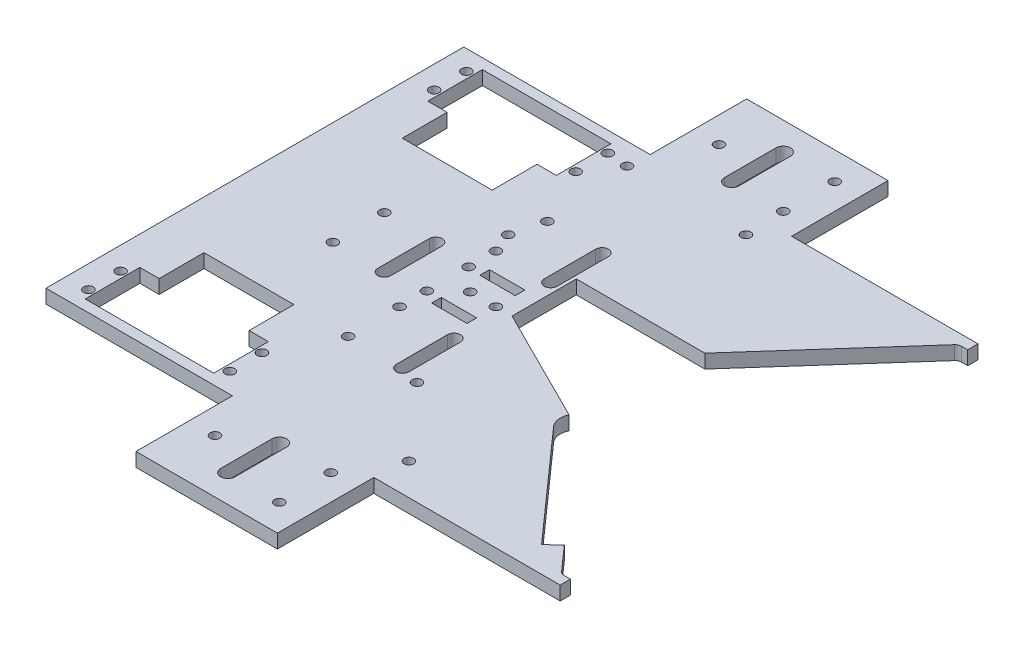
SolidWorks part; units mm, degrees
ref_plane "Front Plane" through (0, 0, 0) normal (0, 0, 1) x (1, 0, 0)
ref_plane "Top Plane" through (0, 0, 0) normal (0, 1, 0) x (1, 0, 0)
ref_plane "Right Plane" through (0, 0, 0) normal (1, 0, 0) x (0, 0, -1)
sketch "Sketch2" plane through (0, 0, 0) normal (0, 1, 0) x (1, 0, 0)
  line L2 (0, 0) -> (0, 65)
  line L3 (0, 65) -> (58, 65)
  line L4 (160, 0) -> (160, 65)
  line L8 (0, 0) -> (160, 0)
  line L9 (102, 65) -> (160, 65)
  line L11 (102, 65) -> (102, 95)
  line L12 (58, 65) -> (58, 95)
  line L13 (58, 95) -> (102, 95)
  dimension "D1" = 65
  dimension "D2" = 160
  dimension "D3" = 44
  dimension "D4" = 30
extrude "Boss-Extrude1" add sketch "Sketch2" along normal blind 4.3
mirror "Mirror1" about plane through (0, 4.3, 0) normal (0, 0, -1) of bodies 101
sketch "Sketch3" plane through (0, 4.3, 0) normal (0, 1, 0) x (1, 0, 0)
  line L0 (160, 61.8) -> (160, -61.8)
  line L1 (120.0126, 20) -> (157.1565, 61.8)
  line L3 (80.0126, 0) -> (80.0126, 20)
  line L4 (80.0126, 20) -> (120.0126, 20)
  line L12 (160, 65) -> (102, 65)
  line L13 (102, 65) -> (102, 95)
  line L15 (102, 95) -> (58, 95)
  line L16 (58, 65) -> (0, 65)
  line L17 (0, 65) -> (0, -65)
  line L18 (0, -65) -> (58, -65)
  line L20 (58, 95) -> (58, 65)
  line L22 (102, -65) -> (160, -65)
  line L23 (160, -65) -> (160, 65)
  line L36 (58, -65) -> (58, -95)
  line L38 (58, -95) -> (102, -95)
  line L39 (58, -95) -> (102, -95)
  line L40 (102, -95) -> (102, -65)
  line L42 (160, -61.8) -> (157.1556, -61.8)
  line L45 (160, 61.8) -> (157.1565, 61.8)
  line L48 (80.0126, 0) -> (120, -20)
  line L49 (120, -20) -> (157.1556, -61.8)
  line M24 (160, -65) -> (160, 65)
  dimension "D2" = 130
  dimension "D3" = 20
  dimension "D4" = 40
  dimension "D1" = 0
extrude "Cut-Extrude1" cut sketch "Sketch3" against normal blind 4.5 contours L48 L49 L1 L4 L3 M24 region at (132.7054, 4.3, -1.1594)
fillet "Fillet1" radius 2 2 edges at (157.1565, 2.15, -61.8) (157.1556, 2.15, 61.8)
ref_axis "Axis1" through (80, 4.3, 95) along (0, 0, -1)
sketch "Sketch4" plane through (0, 4.3, 0) normal (0, 1, 0) x (1, 0, 0)
  line L0 (80, -95) -> (80, 95)
  line L1 (102, -95) -> (58, -95) construction
  line L2 (102, 95) -> (58, 95) construction
ref_plane "Plane2" through (0, 4.3, 0) normal (0, 1, 0) x (1, 0, 0)
sketch "Sketch6" plane through (0, 4.3, 0) normal (0, 1, 0) x (1, 0, 0)
  line L3 (9, -61.8) -> (49, -61.8)
  line L6 (29, -45.8) -> (29, -44.8)
  line L7 (9, -44.8) -> (15, -44.8)
  line L11 (43, -44.8) -> (43, -30.8418)
  line L12 (15, -44.8) -> (15, -30.8418)
  line L13 (15, -30.8418) -> (43, -30.8418)
  line L15 (0, 0) -> (80.0126, 0)
  line L16 (80.0126, 0) -> (120, -20) construction
  line L18 (9, 44.8) -> (15, 44.8)
  line L20 (15, 30.8418) -> (43, 30.8418)
  line L21 (15, 44.8) -> (15, 30.8418)
  line L22 (43, 44.8) -> (43, 30.8418)
  line L25 (15, -45.8) -> (15, -30.8418) construction
  line L27 (9, 61.8) -> (49, 61.8)
  line L30 (4, -61.8) -> (3, -61.8)
  line L31 (0, -61.8) -> (160, -61.8) construction
  line L32 (3, -61.8) -> (4, -61.8)
  line L33 (3, -44.8) -> (3, -62.8) construction
  line L34 (3, -62.8) -> (55, -62.8) construction
  line L35 (55, -44.8) -> (55, -62.8) construction
  line L36 (4, -61.8) -> (54, -61.8) construction
  line L37 (0, 61.8) -> (160, 61.8) construction
  line L38 (54, 61.8) -> (55, 61.8)
  line L39 (54, 61.8) -> (55, 61.8)
  line L40 (43, 44.8) -> (49, 44.8)
  line L41 (4, -45.8) -> (4, -61.8) construction
  line L42 (4, -45.8) -> (54, -45.8) construction
  line L43 (43, -44.8) -> (49, -44.8)
  line L44 (3, -44.8) -> (55, -44.8) construction
  line L45 (29, -45.8) -> (29, -30.8418) construction
  line L46 (43, -45.8) -> (43, -30.8418) construction
  line L47 (54, -45.8) -> (54, -61.8) construction
  line L48 (9, -61.8) -> (49, -61.8)
  line L52 (9, 61.8) -> (9, 44.8)
  line L53 (55, 61.8) -> (54, 61.8)
  line L56 (49, 61.8) -> (49, 44.8)
  line L59 (3, -61.8) -> (4, -61.8)
  line L60 (9, -44.8) -> (9, -61.8)
  line L64 (49, -44.8) -> (49, -61.8)
  dimension "D4" = 1
  dimension "D5" = 14
  dimension "D6" = 14
extrude "Cut-Extrude2" cut sketch "Sketch6" against normal blind 10
sketch "Sketch8" plane through (0, 4.3, 0) normal (0, 1, 0) x (1, 0, 0)
  circle A0 centre (7, 58.8) radius 1.5
  circle A1 centre (7, 48.8) radius 1.5
  circle A2 centre (51, 48.8) radius 1.5
  circle A3 centre (51, 58.8) radius 1.5
  circle A4 centre (7, -48.8) radius 1.5
  circle A5 centre (7, -58.8) radius 1.5
  circle A6 centre (51, -58.8) radius 1.5
  circle A7 centre (51, -48.8) radius 1.5
  dimension "D7" = 3
extrude "Cut-Extrude3" cut sketch "Sketch8" against normal blind 10
sketch "Sketch9" plane through (0, 0, 0) normal (0, -1, 0) x (1, 0, 0)
  line L0 (75.75, 70.4) -> (75.75, 86.4)
  line L1 (75.75, -86.4) -> (75.75, -70.4)
  line L2 (80.25, -86.4) -> (80.25, -70.4)
  line L4 (80.25, 70.4) -> (80.25, 86.4)
  circle A0 centre (94, 70.4) radius 1.5
  circle A1 centre (66, 78.4) radius 1.5
  circle A2 centre (66, -78.4) radius 1.5
  circle A3 centre (94, -86.4) radius 1.5
  circle A4 centre (94, 86.4) radius 1.5
  circle A5 centre (94, -70.4) radius 1.5
  arc A6 (75.75, -86.4) -> (80.25, -86.4) centre (78, -86.4) ccw
  arc A7 (80.25, -70.4) -> (75.75, -70.4) centre (78, -70.4) ccw
  arc A10 (75.75, 70.4) -> (80.25, 70.4) centre (78, 70.4) ccw
  arc A12 (80.25, 86.4) -> (75.75, 86.4) centre (78, 86.4) ccw
  dimension "D1" = 3
extrude "Cut-Extrude4" cut sketch "Sketch9" against normal blind 10
sketch "Sketch7" plane through (0, 4.3, 0) normal (0, 1, 0) x (1, 0, 0)
  line L0 (0, 0) -> (80.0126, 0)
  line L1 (0, 65) -> (0, -65) construction
  line L2 (80.0126, 0) -> (80.0126, 20) construction
  line L3 (80, -95) -> (80, 95) construction
  line L4 (64, -9) -> (75, -9)
  line L5 (64, -6) -> (75, -6)
  line L6 (64, -9) -> (64, -6)
  line L7 (75, -9) -> (75, -6)
  line L8 (64, -7.5) -> (75, -7.5)
  line L9 (64, 7.5) -> (75, 7.5)
  line L10 (75, 9) -> (75, 6)
  line L11 (64, 9) -> (64, 6)
  line L12 (64, 6) -> (75, 6)
  line L13 (64, 9) -> (75, 9)
  circle A0 centre (60.0126, -6.5) radius 1.5
  circle A1 centre (60.0126, 6.5) radius 1.5
  dimension "D1" = 3
  dimension "D2" = 6.5
  dimension "D3" = 20
  dimension "D6" = 11
  dimension "D4" = 5
  dimension "D5" = 3
  dimension "D7" = 7.5
sketch "Sketch10" plane through (0, 4.3, 0) normal (0, 1, 0) x (1, 0, 0)
  line L0 (120, -20) -> (156.5589, -61.1287) construction
  line L1 (123.3218, -23.737) -> (149.8964, -53.6334)
  line L2 (116.263, -23.3218) -> (146.1593, -56.9552)
  line L3 (149.8964, -53.6334) -> (146.1593, -56.9552)
  line L4 (120, -20) -> (156.5589, -61.1287) construction
  line L5 (116.263, -23.3218) -> (152.8218, -64.4505) construction
  arc A0 (123.3218, -23.737) -> (116.263, -23.3218) centre (120, -20) ccw
  dimension "D1" = 5
  dimension "D2" = 45
extrude "Cut-Extrude5" cut sketch "Sketch10" against normal blind 10
sketch "Sketch11" plane through (0, 0, 0) normal (0, -1, 0) x (1, 0, 0)
  line L0 (0, 0) -> (80.0126, 0) construction
  line L1 (80, 95) -> (80, -95) construction
  line L2 (80.0126, 0) -> (0, 0)
  line L4 (75, 31.0313) -> (75, 15.0313)
  line L6 (79, 31.0313) -> (79, 15.0313)
  line L7 (79, -31.0313) -> (79, -15.0313)
  line L8 (75, -31.0313) -> (75, -15.0313)
  circle A0 centre (60, 31) radius 1.5
  circle A1 centre (60, 15) radius 1.5
  arc A2 (75, 31.0313) -> (79, 31.0313) centre (77, 31.0313) cw
  arc A3 (75, 15.0313) -> (79, 15.0313) centre (77, 15.0313) ccw
  arc A4 (75, -15.0313) -> (79, -15.0313) centre (77, -15.0313) cw
  arc A5 (75, -31.0313) -> (79, -31.0313) centre (77, -31.0313) ccw
  circle A6 centre (60, -15) radius 1.5
  circle A7 centre (60, -31) radius 1.5
  dimension "D1" = 3
  dimension "D2" = 16
  dimension "D3" = 15
  dimension "D4" = 20
  dimension "D5" = 15
  dimension "D6" = 4
extrude "Cut-Extrude6" cut sketch "Sketch11" against normal blind 10 contours L4 A3 L6 A2 | L8 A5 L7 A4 | A7 | A0 | A1 | A6 region at (77, 0, 23.0313) region at (77, 0, -23.0313) region at (60, 0, -31)
sketch "Sketch12" plane through (0, 0, 0) normal (0, -1, 0) x (-1, 0, 0)
  line L0 (0, 0) -> (-80.0126, 0) construction
  line L3 (-50.2627, -8) -> (-50.2627, 8)
  line L4 (-50.2627, 0) -> (-46.2627, 0)
  line L5 (-46.2627, -8) -> (-46.2627, 8)
  circle A0 centre (-32.2627, -8) radius 1.5
  circle A1 centre (-32.2627, 8) radius 1.5
  arc A2 (-46.2627, 8) -> (-50.2627, 8) centre (-48.2627, 8) ccw
  arc A3 (-50.2627, -8) -> (-46.2627, -8) centre (-48.2627, -8) ccw
  dimension "D1" = 3
  dimension "D2" = 8
  dimension "D3" = 14
  dimension "D4" = 4
extrude "Cut-Extrude7" cut sketch "Sketch12" against normal blind 10 contours A3 L5 L4 L3 | L4 L5 A2 L3 | A0 | A1 region at (48.2627, 0, 4.7958) region at (48.2627, 0, -4.7958) region at (32.2627, 0, 8) region at (32.2627, 0, -8)
extrude "Cut-Extrude8" cut sketch "Sketch7" against normal blind 9 contours A0 | L4 L7 L5 L6 | L12 L10 L13 L11 | A1
sketch "Sketch13" plane through (0, 4.3, 0) normal (0, 1, 0) x (1, 0, 0)
  line L0 (80.0126, 0) -> (59.0194, 0)
  line L1 (80, -95) -> (80, 95) construction
  circle A0 centre (67, 0) radius 1.5
  circle A1 centre (75, 0) radius 1.5
  dimension "D2" = 3
  dimension "D3" = 5
  dimension "D1" = 8
extrude "Cut-Extrude9" cut sketch "Sketch13" against normal blind 10 contours L0 A0 | L0 A0 | L0 A1 | L0 A1 region at (75, 4.3, 0.6366) region at (75, 4.3, -0.6366) region at (67, 4.3, 0.6366) region at (67, 4.3, -0.6366)
sketch "Sketch14" plane through (0, 4.3, 0) normal (0, 1, 0) x (1, 0, 0)
  circle A0 centre (57.5, 58.3) radius 1.5
  circle A1 centre (94.5, 58.3) radius 1.5
  circle A2 centre (57.5, 21.3) radius 1.5
  circle A3 centre (83.1278, -32.706) radius 1.5
  circle A4 centre (103.0587, -55.1282) radius 1.5
  dimension "D1" = 3
  dimension "D2" = 3
extrude "Cut-Extrude10" cut sketch "Sketch14" against normal blind 10
